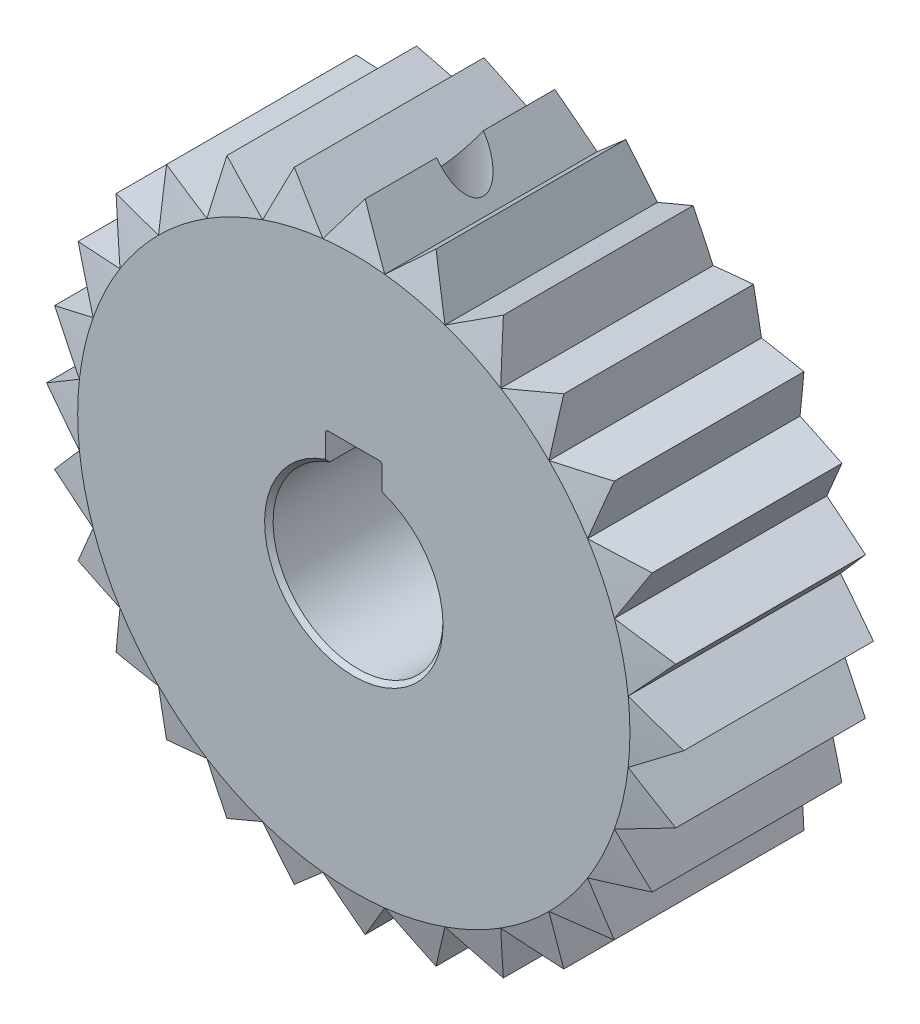
SolidWorks part; units mm, degrees
ref_plane "前视基准面" through (0, 0, 0) normal (0, 0, 1) x (1, 0, 0)
ref_plane "上视基准面" through (0, 0, 0) normal (0, 1, 0) x (1, 0, 0)
ref_plane "右视基准面" through (0, 0, 0) normal (1, 0, 0) x (0, 0, -1)
sketch "草图1" plane through (0, 0, 0) normal (1, 0, 0) x (0, 0, -1)
  line L0 (-15, 19.5) -> (-15, 6.3)
  line L1 (-15, 6.3) -> (-14.7, 6)
  line L2 (-14.7, 6) -> (-0.3, 6)
  line L3 (-0.3, 6) -> (0, 6.3)
  line L4 (0, 6.3) -> (0, 19.5)
  line L5 (0, 19.5) -> (-0.8038, 22.5)
  line L6 (-0.8038, 22.5) -> (-14.1962, 22.5)
  line L7 (-14.1962, 22.5) -> (-15, 19.5)
  line L8 (0, 0) -> (-27, 0) construction
revolve "旋转1" add sketch "草图1" angle 360 about L8 reverse direction yes
sketch "草图2" plane through (0, 0, 0) normal (0, 0, 1) x (1, 0, 0)
  line L0 (-22.5, 0) -> (-19.3774, -2.1833)
  line L1 (-19.3774, -2.1833) -> (-21.9359, -5.0067)
  line L2 (-21.9359, -5.0067) -> (-18.4057, -6.4404)
  line L3 (-18.4057, -6.4404) -> (-20.2718, -9.7624)
  line L4 (-20.2718, -9.7624) -> (-16.5111, -10.3746)
  line L5 (-16.5111, -10.3746) -> (-17.5912, -14.0285)
  line L6 (-17.5912, -14.0285) -> (-13.7886, -13.7886)
  line L7 (-13.7886, -13.7886) -> (-14.0285, -17.5912)
  line L8 (-14.0285, -17.5912) -> (-10.3746, -16.5111)
  line L9 (-10.3746, -16.5111) -> (-9.7624, -20.2718)
  line L10 (-9.7624, -20.2718) -> (-6.4404, -18.4057)
  line L11 (-6.4404, -18.4057) -> (-5.0067, -21.9359)
  line L12 (-5.0067, -21.9359) -> (-2.1833, -19.3774)
  line L13 (-2.1833, -19.3774) -> (0, -22.5)
  line L14 (0, -22.5) -> (2.1833, -19.3774)
  line L15 (2.1833, -19.3774) -> (5.0067, -21.9359)
  line L16 (5.0067, -21.9359) -> (6.4404, -18.4057)
  line L17 (6.4404, -18.4057) -> (9.7624, -20.2718)
  line L18 (9.7624, -20.2718) -> (10.3746, -16.5111)
  line L19 (10.3746, -16.5111) -> (14.0285, -17.5912)
  line L20 (14.0285, -17.5912) -> (13.7886, -13.7886)
  line L21 (13.7886, -13.7886) -> (17.5912, -14.0285)
  line L22 (17.5912, -14.0285) -> (16.5111, -10.3746)
  line L23 (16.5111, -10.3746) -> (20.2718, -9.7624)
  line L24 (20.2718, -9.7624) -> (18.4057, -6.4404)
  line L25 (18.4057, -6.4404) -> (21.9359, -5.0067)
  line L26 (21.9359, -5.0067) -> (19.3774, -2.1833)
  line L27 (19.3774, -2.1833) -> (22.5, 0)
  line L28 (22.5, 0) -> (19.3774, 2.1833)
  line L29 (19.3774, 2.1833) -> (21.9359, 5.0067)
  line L30 (21.9359, 5.0067) -> (18.4057, 6.4404)
  line L31 (18.4057, 6.4404) -> (20.2718, 9.7624)
  line L32 (20.2718, 9.7624) -> (16.5111, 10.3746)
  line L33 (16.5111, 10.3746) -> (17.5912, 14.0285)
  line L34 (17.5912, 14.0285) -> (13.7886, 13.7886)
  line L35 (13.7886, 13.7886) -> (14.0285, 17.5912)
  line L36 (14.0285, 17.5912) -> (10.3746, 16.5111)
  line L37 (10.3746, 16.5111) -> (9.7624, 20.2718)
  line L38 (9.7624, 20.2718) -> (6.4404, 18.4057)
  line L39 (6.4404, 18.4057) -> (5.0067, 21.9359)
  line L40 (5.0067, 21.9359) -> (2.1833, 19.3774)
  line L41 (2.1833, 19.3774) -> (0, 22.5)
  line L42 (0, 22.5) -> (-2.1833, 19.3774)
  line L43 (-2.1833, 19.3774) -> (-5.0067, 21.9359)
  line L44 (-5.0067, 21.9359) -> (-6.4404, 18.4057)
  line L45 (-6.4404, 18.4057) -> (-9.7624, 20.2718)
  line L46 (-9.7624, 20.2718) -> (-10.3746, 16.5111)
  line L47 (-10.3746, 16.5111) -> (-14.0285, 17.5912)
  line L48 (-14.0285, 17.5912) -> (-13.7886, 13.7886)
  line L49 (-13.7886, 13.7886) -> (-17.5912, 14.0285)
  line L50 (-17.5912, 14.0285) -> (-16.5111, 10.3746)
  line L51 (-16.5111, 10.3746) -> (-20.2718, 9.7624)
  line L52 (-20.2718, 9.7624) -> (-18.4057, 6.4404)
  line L53 (-18.4057, 6.4404) -> (-21.9359, 5.0067)
  line L54 (-21.9359, 5.0067) -> (-19.3774, 2.1833)
  line L55 (-19.3774, 2.1833) -> (-22.5, 0)
  circle A0 centre (0, 0) radius 45
extrude "切除-拉伸1" cut sketch "草图2" along normal blind 15
ref_plane "基准面1" through (0, 0, 15) normal (0, 0, 1) x (1, 0, 0)
ref_plane "基准面2" through (0, 0, 22) normal (0, 0, 1) x (1, 0, 0)
sketch "草图3" plane through (0, 0, 0) normal (0, 0, 1) x (1, 0, 0)
  line L0 (-2, 0) -> (2, 0)
  line L1 (2, 0) -> (2, 7.6)
  line L2 (1.8, 7.8) -> (-1.8, 7.8)
  line L3 (-2, 7.6) -> (-2, 0)
  arc A0 (2, 7.6) -> (1.8, 7.8) centre (1.8, 7.6) ccw
  arc A1 (-1.8, 7.8) -> (-2, 7.6) centre (-1.8, 7.6) ccw
extrude "切除-拉伸2" cut sketch "草图3" along normal blind 27
ref_plane "基准面3" through (0, 0, 0) normal (0.7071, -0.7071, 0) x (0, 0, -1)
ref_plane "基准面4" through (0, 0, 15) normal (0, 0, 1) x (1, 0, 0)
ref_plane "基准面5" through (0, 17, 0) normal (0, 1, 0) x (1, 0, 0)
ref_plane "b XY" through (0, 0, 0) normal (0, 0, 1) x (1, 0, 0)
ref_plane "b XZ" through (0, 0, 0) normal (0, -1, 0) x (-1, 0, 0)
ref_plane "b YZ" through (0, 0, 0) normal (1, 0, 0) x (0, 0, -1)
ref_axis "b X" through (-80.9, 0, 0) along (1, 0, 0)
ref_axis "b Y" through (0, -50, 0) along (0, 1, 0)
ref_axis "b Z" through (0, 0, 80.9) along (0, 0, -1)
sketch3d "b"
  point P0 (0, 0, 0)
ref_plane "screw XY" through (0, 17, 0) normal (0, 1, 0) x (1, 0, 0)
ref_plane "screw XZ" through (0, 0, 22) normal (0, 0, 1) x (1, 0, 0)
ref_plane "screw YZ" through (0, 0, 0) normal (1, 0, 0) x (0, 0, -1)
ref_axis "screw X" through (-80.9, 17, 22) along (1, 0, 0)
ref_axis "screw Y" through (0, 17, 50) along (0, 0, -1)
ref_axis "screw Z" through (0, 50, 22) along (0, -1, 0)
sketch3d "screw"
  point P0 (0, 17, 22)
ref_plane "turn_around XY" through (0, 0, 0) normal (-1, 0, 0) x (0, 0, 1)
ref_plane "turn_around XZ" through (0, 0, 0) normal (0, 1, 0) x (1, 0, 0)
ref_plane "turn_around YZ" through (0, 0, 0) normal (0, 0, -1) x (-1, 0, 0)
ref_axis "turn_around X" through (0, 0, 80.9) along (0, 0, -1)
ref_axis "turn_around Y" through (0, 50, 0) along (0, -1, 0)
ref_axis "turn_around Z" through (-80.9, 0, 0) along (1, 0, 0)
sketch3d "turn_around"
  point P0 (0, 0, 0)
hole_wizard "M4 螺纹孔1" positions "草图5" profile "草图4" tap size "M4" standard "GB" end condition through all
sketch "草图5" plane through (0, 7.8, 0) normal (0, -1, 0) x (-1, 0, 0)
  line L0 (-1.8, -15) -> (1.8, -15) construction
  line L1 (2, -14.7) -> (2, -0.3) construction
  point P0 (0, -7.5)
  dimension "D1" = 7.5
  dimension "D2" = 2
cosmetic thread "孔螺蚊线1"
sketch "草图4" plane through (0, 7.8, 7.5) normal (1, 0, 0) x (0, 0, -1)
  line L0 (0, 0) -> (0, 14.7)
  line L1 (0, 14.7) -> (1.65, 14.7)
  line L2 (1.65, 14.7) -> (1.65, 0)
  line L5 (1.65, 0) -> (0, 0)
  line L11 (0, -6.35) -> (0, 107.95) construction
  dimension "通孔螺纹孔钻头直径" = 3.3
  dimension "通孔螺纹孔钻头深度" = 14.7
